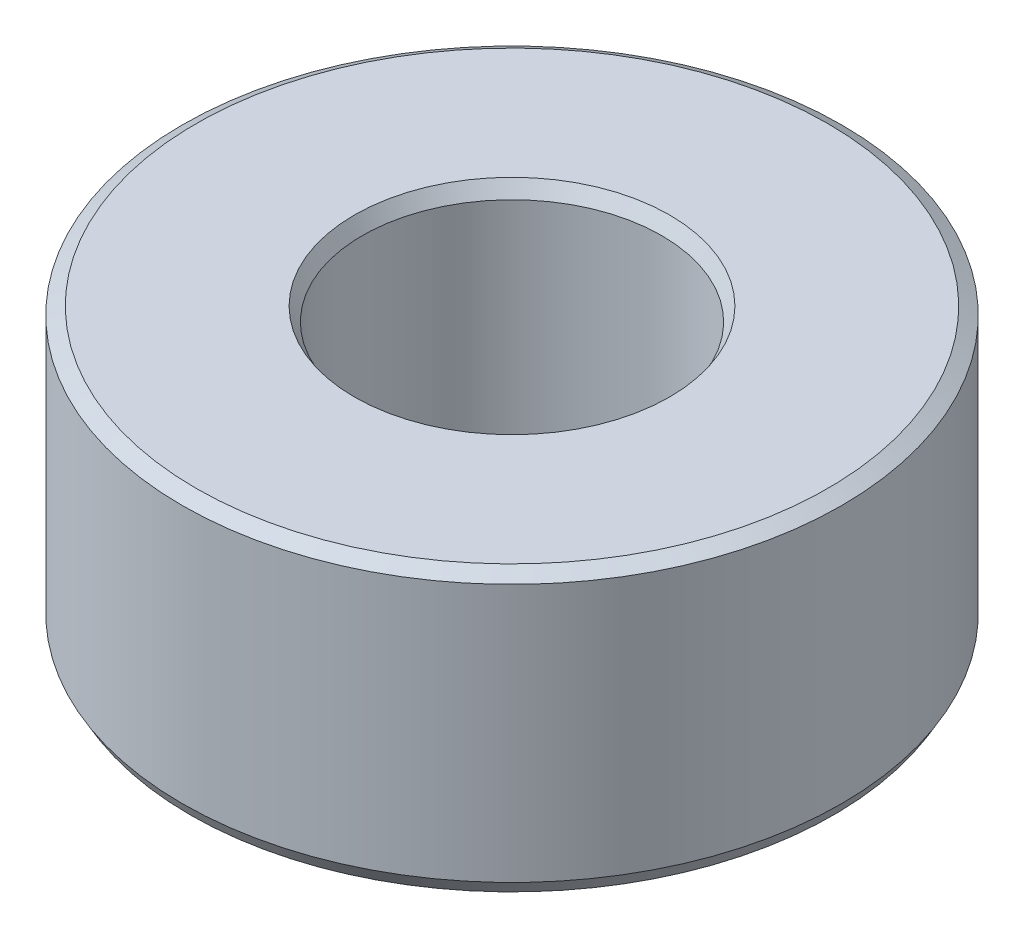
SolidWorks part; units mm, degrees
ref_plane "Front Plane" through (0, 0, 0) normal (0, 0, 1) x (1, 0, 0)
ref_plane "Top Plane" through (0, 0, 0) normal (0, 1, 0) x (1, 0, 0)
ref_plane "Right Plane" through (0, 0, 0) normal (1, 0, 0) x (0, 0, -1)
sketch "Sketch1" plane through (0, 0, 0) normal (0, 1, 0) x (1, 0, 0)
  circle A0 centre (0, 0) radius 45
  dimension "SLEEVE_OD" = 90
extrude "Boss-Extrude1" add sketch "Sketch1" along normal blind 38.2073
sketch "Sketch2" plane through (0, 0, 0) normal (0, 1, 0) x (1, 0, 0)
  circle A0 centre (0, 0) radius 20.4281
  dimension "BORE_D" = 40.8562
extrude "Cut-Extrude1" cut sketch "Sketch2" along normal through all
chamfer "Chamfer1" distance 1.0882 angle 60 4 edges at (0, 38.2073, 20.4281) (0, 0, 20.4281) (0, 0, 45) (0, 38.2073, 45) first distance on face at (0, 38.2073, 20.4281) first distance on face at (0, 0, 20.4281) first distance on face at (0, 38.2073, 45)
